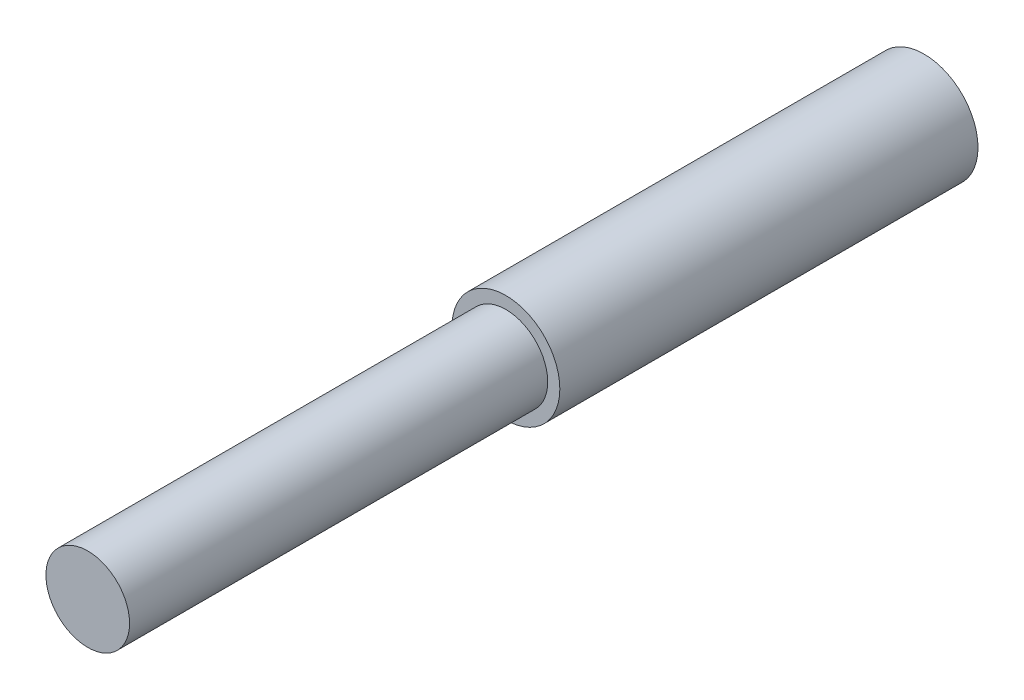
SolidWorks part; units mm, degrees
material "AISI 1020"
ref_plane "Front Plane" through (0, 0, 0) normal (0, 0, 1) x (1, 0, 0)
ref_plane "Top Plane" through (0, 0, 0) normal (0, 1, 0) x (1, 0, 0)
ref_plane "Right Plane" through (0, 0, 0) normal (1, 0, 0) x (0, 0, -1)
sketch "Sketch1" plane through (0, 0, 0) normal (0, 0, 1) x (1, 0, 0)
  circle A0 centre (0, 0) radius 6.223
  dimension "D1" = 12.446
extrude "Boss-Extrude1" add sketch "Sketch1" along normal blind 48.26
sketch "Sketch2" plane through (0, 0, 48.26) normal (0, 0, 1) x (1, 0, 0)
  circle A0 centre (0, 0) radius 4.826
  dimension "D1" = 9.652
extrude "Boss-Extrude2" add sketch "Sketch2" along normal blind 48.26
